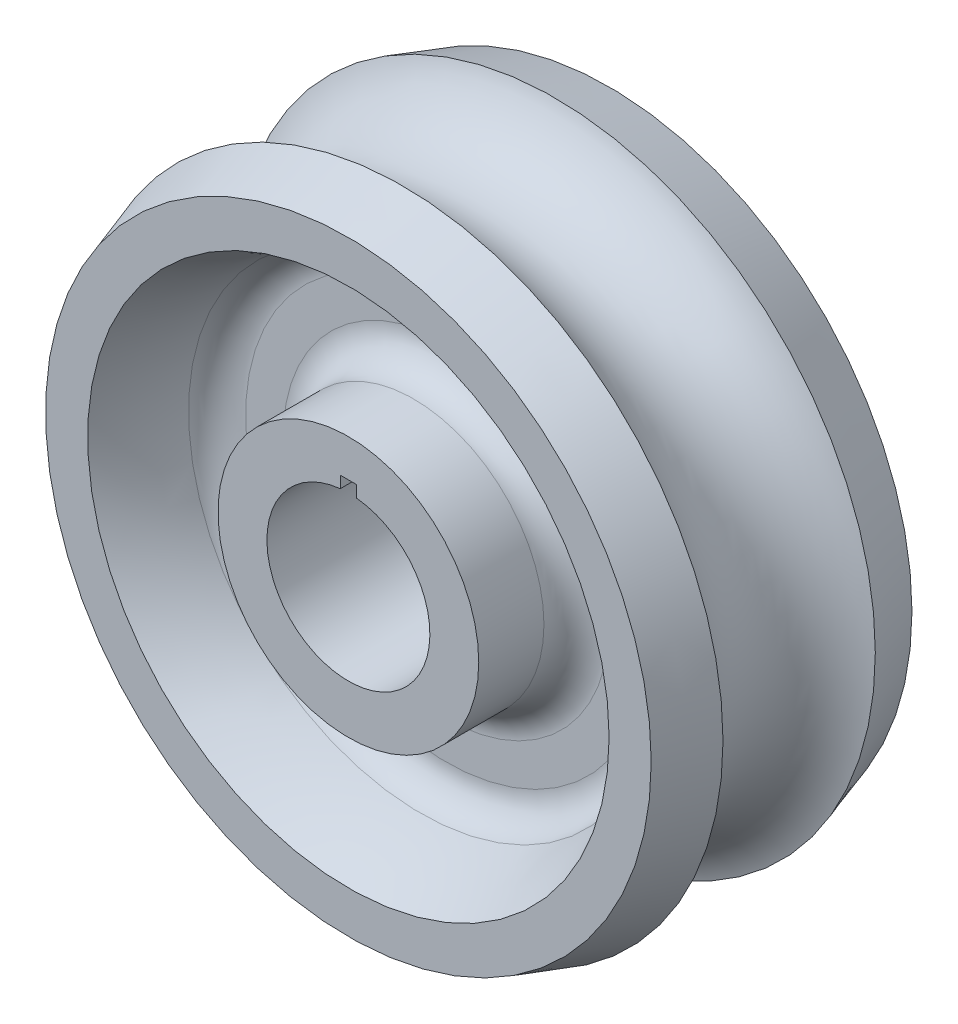
SolidWorks part; units mm, degrees
material "PW20:29:Sc:0:"
ref_plane "Front" through (0, 0, 0) normal (0, 0, 1) x (1, 0, 0)
ref_plane "Top" through (0, 0, 0) normal (0, 1, 0) x (1, 0, 0)
ref_plane "Right" through (0, 0, 0) normal (1, 0, 0) x (0, 0, -1)
sketch "Sketch1" plane through (0, 0, 0) normal (1, 0, 0) x (0, 0, -1)
  line L0 (0, 0) -> (159.8623, 0) construction
  line L1 (0, 0) -> (0, 93.2897) construction
  line L2 (-12.7, 7.9375) -> (12.7, 7.9375)
  line L3 (12.7, 7.9375) -> (12.7, 12.7)
  line L4 (12.7, 12.7) -> (6.35, 12.7)
  line L5 (3.175, 15.875) -> (3.175, 19.5365)
  line L6 (12.7, 25.4) -> (12.7, 29.5021)
  line L7 (12.7, 29.5021) -> (7.4182, 31.2134)
  line L8 (-12.7, 29.5021) -> (-7.4182, 31.2134)
  line L9 (-12.7, 25.4) -> (-12.7, 29.5021)
  line L10 (-3.175, 15.875) -> (-3.175, 19.5365)
  line L11 (-12.7, 12.7) -> (-6.35, 12.7)
  line L12 (-12.7, 7.9375) -> (-12.7, 12.7)
  arc A0 (6.35, 12.7) -> (3.175, 15.875) centre (6.35, 15.875) cw
  arc A1 (3.175, 19.5365) -> (5.6444, 22.6321) centre (6.35, 19.5365) cw
  arc A2 (5.6444, 22.6321) -> (12.7, 25.4) centre (0, 47.397) ccw
  arc A3 (7.4182, 31.2134) -> (-7.4182, 31.2134) centre (0, 33.6169) cw
  arc A4 (-5.6444, 22.6321) -> (-12.7, 25.4) centre (0, 47.397) cw
  arc A5 (-3.175, 19.5365) -> (-5.6444, 22.6321) centre (-6.35, 19.5365) ccw
  arc A6 (-6.35, 12.7) -> (-3.175, 15.875) centre (-6.35, 15.875) ccw
  point P29 (0, 7.9375)
  dimension "D1" = 25.4
  dimension "D2" = 3.175
  dimension "D4" = 7.7978
  dimension "D9" = 25.4
  dimension "D3" = 50.8
  dimension "D5" = 6.35
  dimension "D6" = 4.7625
  dimension "D7" = 15.875
  dimension "D8" = 21.5646
  dimension "D10" = 67.2338
revolve "Base-Revolve" add sketch "Sketch1" angle 360 about L0
sketch "Sketch2" plane through (0, 0, 12.7) normal (0, 0, 1) x (1, 0, 0)
  line L0 (0, 0) -> (0, 10.5711) construction
  line L1 (-0.7937, 7.8977) -> (-0.7937, 9.0424)
  line L2 (0.7937, 7.8977) -> (0.7937, 9.0424)
  line L3 (-0.7937, 9.0424) -> (0.7937, 9.0424)
  circle A0 centre (0, 0) radius 7.9375 construction
  arc A1 (0.7937, 7.8977) -> (-0.7937, 7.8977) centre (0, 0) ccw
  dimension "D1" = 1.5875
  dimension "D2" = 9.0424
extrude "Cut-Extrude1" cut sketch "Sketch2" against normal through all
ref_axis "Worm CL" through (0, 0, 50) along (0, 0, -1)
